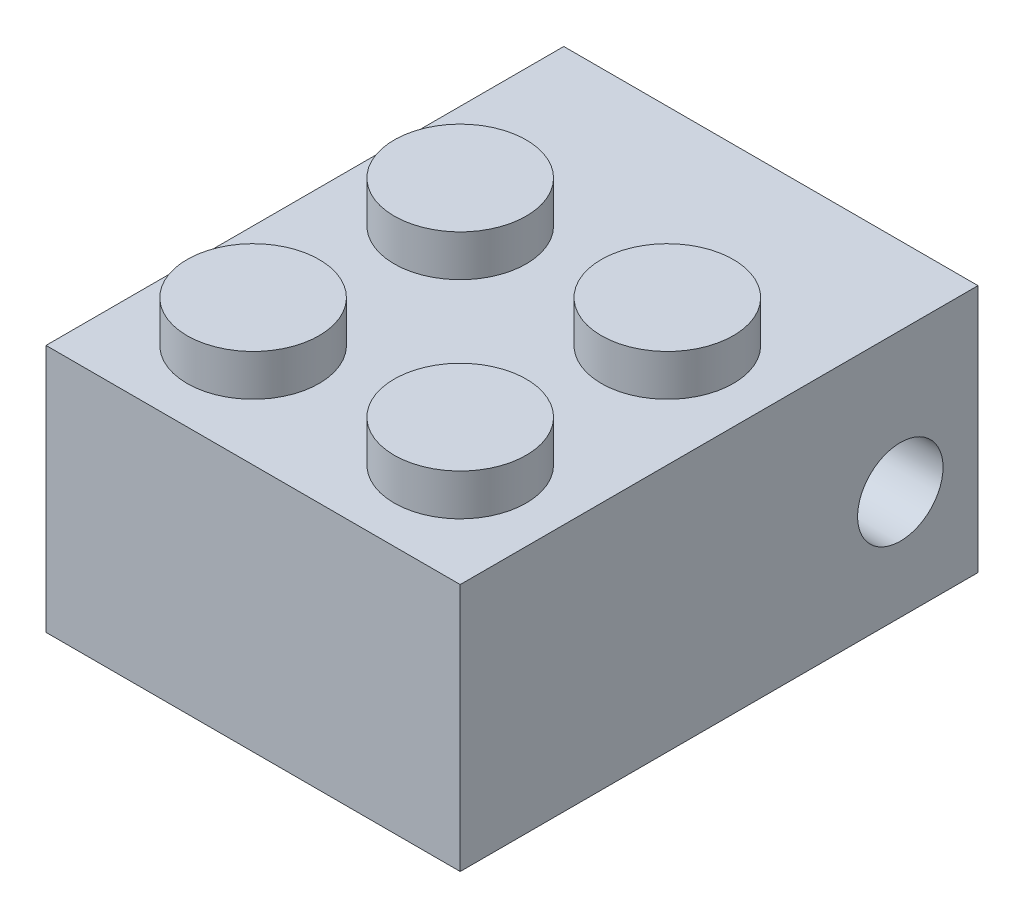
SolidWorks part; units mm, degrees
material "ABS"
ref_plane "Front Plane" through (0, 0, 0) normal (0, 0, 1) x (1, 0, 0)
ref_plane "Top Plane" through (0, 0, 0) normal (0, 1, 0) x (1, 0, 0)
ref_plane "Right Plane" through (0, 0, 0) normal (1, 0, 0) x (0, 0, -1)
sketch "Sketch1" plane through (76, 0, 0) normal (1, 0, 0) x (0, 0, -1)
  line L0 (41.2674, -14.7525) -> (-6.7326, -14.7525) construction
  line L1 (41.2674, -14.7525) -> (-6.7326, -14.7525)
  line L2 (41.2674, -14.7525) -> (45.2674, -14.7525)
  line L3 (45.2674, -14.7525) -> (45.2674, -5.1525)
  line L4 (45.2674, -5.1525) -> (25.2674, -5.1525)
  line L5 (25.2674, -5.1525) -> (25.2674, -14.7525)
  arc A0 (42.2674, -11.8775) -> (42.2674, -9.2275) centre (42.2674, -10.5525) ccw construction
  arc A1 (42.2674, -11.8775) -> (42.2674, -9.2275) centre (42.2674, -10.5525) ccw construction
  circle A2 centre (42.2674, -10.5525) radius 1.65
  line M3 (41.2674, -14.7525) -> (-6.7326, -14.7525)
  dimension "D3" = 3.3
  dimension "D1" = 16
  dimension "D2" = 9.6
  dimension "D4" = 4
extrude "Boss-Extrude1" add sketch "Sketch1" against normal blind 16 contours L4 L5 L2 L3 A2 M3 region at (76, -9.9246, -34.941)
sketch "Sketch2" plane through (0, -5.1525, 0) normal (0, 1, 0) x (1, 0, 0)
  circle A0 centre (64, 29.2674) radius 2.4 construction
  circle A1 centre (72, 29.2674) radius 2.4 construction
  circle A2 centre (72, 37.2674) radius 2.4 construction
  circle A3 centre (64, 37.2674) radius 2.4 construction
  circle A4 centre (64, 29.2674) radius 2.4 construction
  circle A5 centre (72, 29.2674) radius 2.4 construction
  circle A6 centre (72, 37.2674) radius 2.4 construction
  circle A7 centre (64, 37.2674) radius 2.4 construction
  circle A8 centre (64, 37.2674) radius 2.55
  circle A10 centre (72, 37.2674) radius 2.55
  circle A12 centre (72, 29.2674) radius 2.55
  circle A14 centre (64, 29.2674) radius 2.55
  dimension "D1" = 0.15
extrude "Boss-Extrude2" add sketch "Sketch2" along normal blind 1.6
extrude "Cut-Extrude1" cut sketch "Sketch2<2>" along normal blind 1.7 from surface contours A12 | A14 | A8 | A10 region at (64, -5.1525, -37.2674) region at (72, -5.1525, -37.2674) region at (72, -5.1525, -29.2674) region at (64, -5.1525, -29.2674) starting at face at (68, -14.7525, -35.2674)
sketch "Sketch2<2>" plane through (0, -5.1525, 0) normal (0, 1, 0) x (1, 0, 0) same geometry as "Sketch2"
